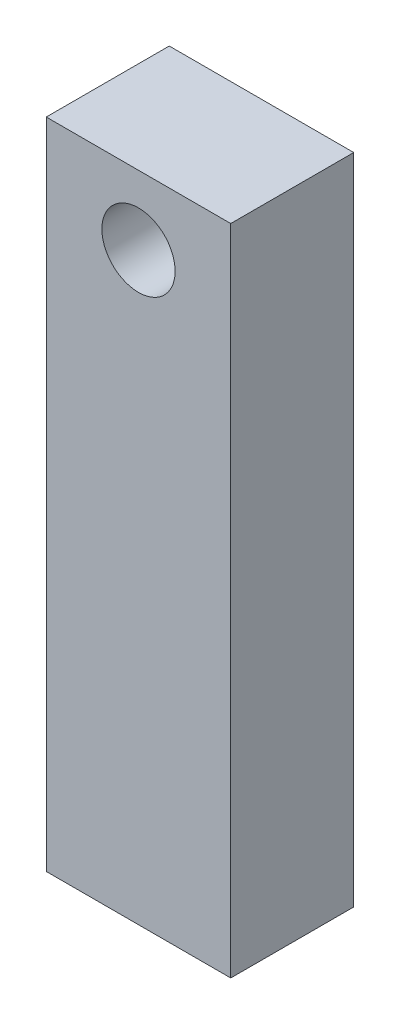
SolidWorks part; units mm, degrees
material "Gray Cast Iron"
ref_plane "Front Plane" through (0, 0, 0) normal (0, 0, 1) x (1, 0, 0)
ref_plane "Top Plane" through (0, 0, 0) normal (0, 1, 0) x (1, 0, 0)
ref_plane "Right Plane" through (0, 0, 0) normal (1, 0, 0) x (0, 0, -1)
sketch "Sketch1" plane through (0, 0, 0) normal (0, 1, 0) x (1, 0, 0)
  line L0 (-12, -8) -> (12, -8)
  line L1 (12, -8) -> (12, 8)
  line L2 (12, 8) -> (-12, 8)
  line L3 (-12, 8) -> (-12, -8)
extrude "Boss-Extrude1" add sketch "Sketch1" along normal blind 85
sketch "Sketch2" plane through (0, 0, 0) normal (0, 0, 1) x (1, 0, 0)
  circle A0 centre (0, 76) radius 4.7625
  dimension "D1" = 9.525
extrude "Cut-Extrude1" cut sketch "Sketch2" against normal mid plane 20
